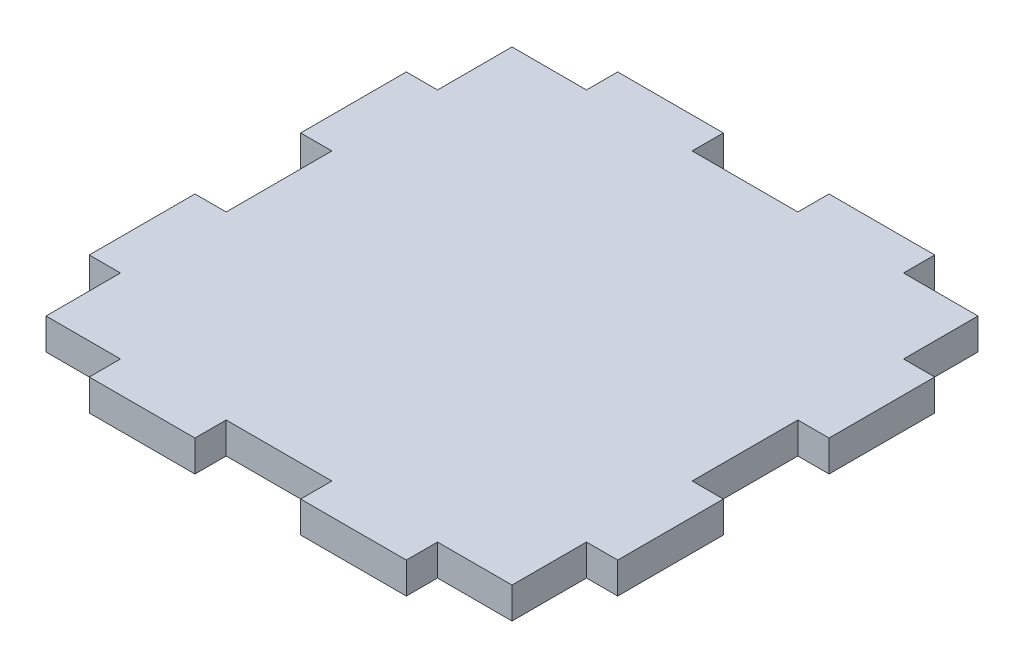
SolidWorks part; units mm, degrees
ref_plane "Front Plane" through (0, 0, 0) normal (0, 0, 1) x (1, 0, 0)
ref_plane "Top Plane" through (0, 0, 0) normal (0, 1, 0) x (1, 0, 0)
ref_plane "Right Plane" through (0, 0, 0) normal (1, 0, 0) x (0, 0, -1)
sketch "Sketch1" plane through (0, 0, 0) normal (0, 1, 0) x (1, 0, 0)
  line L1 (0, 0) -> (50.8, 0)
  line L2 (0, 0) -> (0, 50.8)
  line L3 (0, 50.8) -> (50.8, 50.8)
  line L4 (50.8, 0) -> (50.8, 50.8)
  dimension "D1" = 50.8
extrude "Boss-Extrude1" add sketch "Sketch1" along normal blind 3
sketch "Sketch2" plane through (0, 3, 0) normal (0, 1, 0) x (1, 0, 0)
  line L0 (50.8, 50.8) -> (0, 50.8) construction
  line L1 (40.64, 50.8) -> (50.8, 50.8)
  line L2 (40.64, 50.8) -> (40.64, 47.8)
  line L3 (40.64, 47.8) -> (50.8, 47.8)
  line L4 (50.8, 50.8) -> (50.8, 47.8)
  line L5 (50.8, 0) -> (50.8, 50.8) construction
  line L6 (25.4, 50.8) -> (25.4, 0) construction
  line L7 (20.32, 50.8) -> (30.48, 50.8)
  line L8 (20.32, 50.8) -> (20.32, 47.8)
  line L9 (20.32, 47.8) -> (30.48, 47.8)
  line L10 (30.48, 50.8) -> (30.48, 47.8)
  line L11 (0, 50.8) -> (10.16, 50.8)
  line L12 (0, 50.8) -> (0, 47.8)
  line L13 (0, 47.8) -> (10.16, 47.8)
  line L14 (10.16, 50.8) -> (10.16, 47.8)
  line L15 (0, 0) -> (50.8, 0) construction
  line L16 (0, 25.4) -> (50.8, 25.4) construction
  line L17 (0, 50.8) -> (0, 0) construction
  line L18 (10.16, 47.8) -> (20.32, 47.8) construction
  line L19 (30.48, 47.8) -> (40.64, 47.8) construction
  line L20 (50.8, 0) -> (50.8, 3)
  line L21 (50.8, 47.8) -> (47.8, 47.8)
  line L22 (50.8, 47.8) -> (50.8, 40.64)
  line L23 (50.8, 40.64) -> (47.8, 40.64)
  line L24 (47.8, 47.8) -> (47.8, 40.64)
  line L25 (50.8, 30.48) -> (47.8, 30.48)
  line L26 (50.8, 30.48) -> (50.8, 20.32)
  line L27 (50.8, 20.32) -> (47.8, 20.32)
  line L28 (47.8, 30.48) -> (47.8, 20.32)
  line L29 (50.8, 30.48) -> (47.8, 30.48)
  line L30 (50.8, 30.48) -> (50.8, 20.32)
  line L31 (50.8, 20.32) -> (47.8, 20.32)
  line L32 (47.8, 30.48) -> (47.8, 20.32)
  line L33 (40.64, 0) -> (50.8, 0)
  line L34 (40.64, 3) -> (50.8, 3)
  line L35 (40.64, 0) -> (40.64, 3)
  line L36 (30.48, 0) -> (30.48, 3)
  line L37 (20.32, 0) -> (30.48, 0)
  line L38 (20.32, 3) -> (30.48, 3)
  line L39 (20.32, 0) -> (20.32, 3)
  line L40 (10.16, 0) -> (10.16, 3)
  line L41 (0, 0) -> (10.16, 0)
  line L42 (0, 3) -> (10.16, 3)
  line L43 (0, 0) -> (0, 3)
  line L44 (49.3, 40.64) -> (49.3, 50.8) construction
  line L45 (47.8, 10.16) -> (50.8, 10.16)
  line L46 (47.8, 10.16) -> (47.8, 3)
  line L47 (47.8, 3) -> (50.8, 3)
  line L48 (50.8, 10.16) -> (50.8, 3)
  line L49 (47.8, 40.64) -> (47.8, 30.48) construction
  line L50 (47.8, 20.32) -> (47.8, 30.48) construction
  line L51 (47.8, 20.32) -> (47.8, 10.16) construction
  line L52 (49.3, 10.16) -> (49.3, 0) construction
  line L53 (3, 3) -> (0, 3)
  line L54 (3, 10.16) -> (0, 10.16)
  line L55 (0, 10.16) -> (0, 3)
  line L56 (3, 10.16) -> (3, 3)
  line L57 (0, 20.32) -> (3, 20.32)
  line L58 (0, 30.48) -> (0, 20.32)
  line L59 (0, 30.48) -> (3, 30.48)
  line L60 (3, 30.48) -> (3, 20.32)
  line L61 (0, 40.64) -> (3, 40.64)
  line L62 (3, 47.8) -> (3, 40.64)
  line L63 (0, 47.8) -> (0, 40.64)
  line L64 (0, 47.8) -> (3, 47.8)
  line M33 (0, 50.8) -> (0, 0)
  line M34 (0, 0) -> (50.8, 0)
  line M35 (50.8, 0) -> (50.8, 50.8)
  line M36 (50.8, 50.8) -> (0, 50.8)
  dimension "D1" = 3
  dimension "D2" = 3
extrude "Cut-Extrude1" cut sketch "Sketch2" against normal through all contours L62 L13 L61 M33 | L14 L13 M36 M33 | L10 L8 L9 M36 | L2 L3 M35 M36 | L3 L24 L23 M35 | L25 L28 L27 M35 | L45 L46 L34 M35 | L35 L34 M34 M35 | L39 L36 L38 M34 | L42 L40 M33 M34 | L56 L54 L42 M33 | L60 L59 L57 M33 region at (45.72, 3, -49.3) region at (25.4, 3, -49.3) region at (49.3, 3, -44.22) region at (5.08, 3, -49.3) region at (49.3, 3, -25.4) region at (1.5, 3, -44.22) region at (49.3, 3, -6.58) region at (45.72, 3, -1.5) region at (1.5, 3, -25.4) region at (1.5, 3, -6.58) region at (25.4, 3, -1.5) region at (5.08, 3, -1.5)
